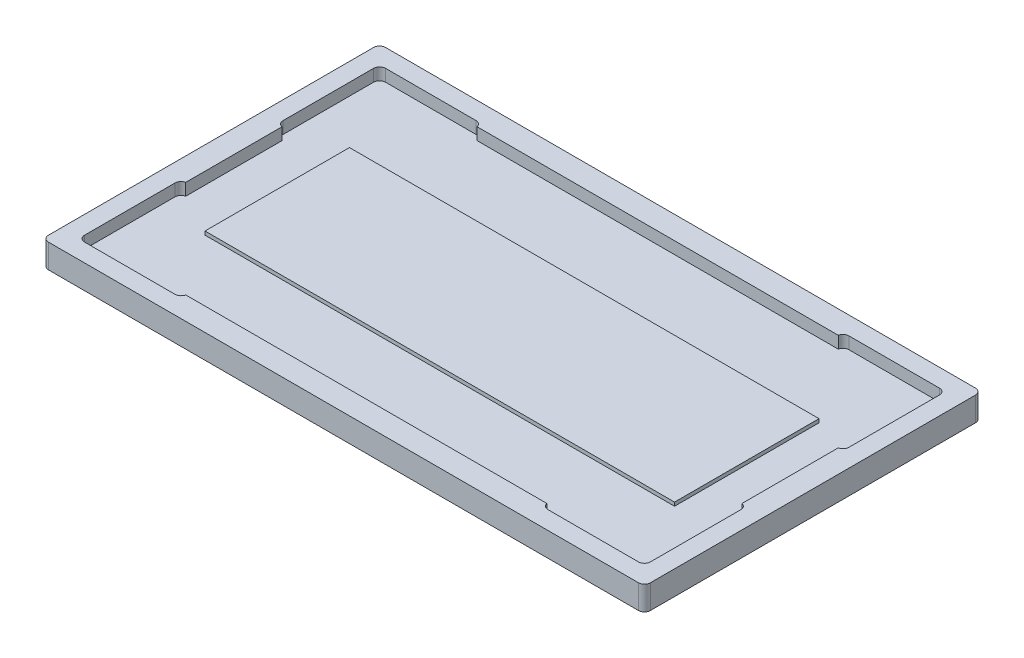
SolidWorks part; units mm, degrees
material "铜"
ref_plane "前视基准面" through (0, 0, 0) normal (0, 0, 1) x (1, 0, 0)
ref_plane "上视基准面" through (0, 0, 0) normal (0, 1, 0) x (1, 0, 0)
ref_plane "右视基准面" through (0, 0, 0) normal (1, 0, 0) x (0, 0, -1)
sketch "草图1" plane through (0, 0, 0) normal (0, 1, 0) x (1, 0, 0)
  line L1 (0, 0) -> (46, 0) construction
  line L2 (0, 0) -> (0, -24) construction
  line L3 (0, -24) -> (46, -24) construction
  line L4 (46, 0) -> (46, -24) construction
  line L5 (-2, 2) -> (48, 2)
  line L6 (-2, 2) -> (-2, -26)
  line L7 (-2, -26) -> (48, -26)
  line L8 (48, 2) -> (48, -26)
  dimension "D1" = 24
  dimension "D2" = 46
  dimension "D3" = 2
  dimension "D4" = 2
  dimension "D5" = 2
  dimension "D6" = 2
extrude "凸台-拉伸1" add sketch "草图1" along normal blind 6
sketch "草图3" plane through (0, 6, 0) normal (0, 1, 0) x (1, 0, 0)
  line L0 (-2, 2) -> (-2, -26) construction
  line L1 (-0.5, 0.5) -> (8, 0.5)
  line L2 (-0.5, 0.5) -> (-0.5, -8)
  line L3 (-0.5, -24.5) -> (8, -24.5)
  line L4 (46.5, 0.5) -> (46.5, -8)
  line L5 (48, -26) -> (48, 2) construction
  line L6 (-2, -26) -> (48, -26) construction
  line L7 (48, 2) -> (-2, 2) construction
  line L8 (-2, -26) -> (48, -26) construction
  line L9 (-0.5, -8) -> (-0.1, -8)
  line L11 (-0.5, -16) -> (-0.1, -16)
  line L12 (-0.1, -8) -> (-0.1, -16)
  line L13 (-0.5, -16) -> (-0.5, -24.5)
  line L14 (46.5, -16) -> (46.5, -24.5)
  line L15 (46.5, -8) -> (46.1, -8)
  line L17 (46.5, -16) -> (46.1, -16)
  line L18 (46.1, -8) -> (46.1, -16)
  line L19 (-2, 2) -> (-2, -26) construction
  line L21 (8, 0.5) -> (8, 0.1)
  line L22 (8, 0.1) -> (38, 0.1)
  line L23 (38, 0.5) -> (38, 0.1)
  line L25 (8, -24.5) -> (8, -24.1)
  line L26 (8, -24.1) -> (38, -24.1)
  line L27 (38, -24.5) -> (38, -24.1)
  line L28 (38, 0.5) -> (46.5, 0.5)
  line L29 (38, -24.5) -> (46.5, -24.5)
  dimension "D1" = 1.5
  dimension "D2" = 1.5
  dimension "D3" = 1.5
  dimension "D4" = 1.5
  dimension "D5" = 10
  dimension "D6" = 10
  dimension "D7" = 10
  dimension "D8" = 10
  dimension "D9" = 10
  dimension "D10" = 10
extrude "切除-拉伸1" cut sketch "草图3" against normal blind 1
fillet "圆角3" radius 0.5 12 edges at (38, 5.5, -0.5) (46.5, 5.5, 8) (46.5, 5.5, -0.5) (46.5, 5.5, 16) (46.5, 5.5, 24.5) (38, 5.5, 24.5) (8, 5.5, 24.5) (-0.5, 5.5, 24.5) (-0.5, 5.5, 16) (-0.5, 5.5, 8) (8, 5.5, -0.5) (-0.5, 5.5, -0.5)
sketch "草图5" plane through (0, 0, 0) normal (0, -1, 0) x (-1, 0, 0)
  line L0 (-48, -26) -> (-48, 2) construction
  line L9 (-43, -5.5) -> (-3, -5.5)
  line L10 (-43, -5.5) -> (-43, -18.5)
  line L11 (-43, -18.5) -> (-3, -18.5)
  line L12 (-3, -5.5) -> (-3, -18.5)
  line L13 (2, 2) -> (2, -26) construction
  line L14 (-48, 2) -> (2, 2) construction
  line L15 (2, -26) -> (-48, -26) construction
  dimension "D1" = 5
  dimension "D2" = 5
  dimension "D3" = 7.5
  dimension "D4" = 7.5
extrude "切除-拉伸2" cut sketch "草图5" against normal blind 4 flip side to cut
fillet "圆角1" radius 0.5 8 edges at (-2, 5, -2) (48, 5, -2) (-2, 5, 26) (48, 5, 26) (43, 2, 5.5) (3, 2, 5.5) (3, 2, 18.5) (43, 2, 18.5)
sketch "草图6" plane through (0, 5, 0) normal (0, 1, 0) x (1, 0, 0)
  line L0 (-0.5, -16.4899) -> (-0.5, -24) construction
  line L1 (42.5, -18) -> (3.5, -18)
  line L2 (42.5, -18) -> (42.5, -6)
  line L3 (42.5, -6) -> (3.5, -6)
  line L4 (3.5, -18) -> (3.5, -6)
  line L6 (0, -24.5) -> (7.5101, -24.5) construction
  dimension "D1" = 4
  dimension "D2" = 6.5
extrude "凸台-拉伸2" add sketch "草图6" along normal blind 0.3
